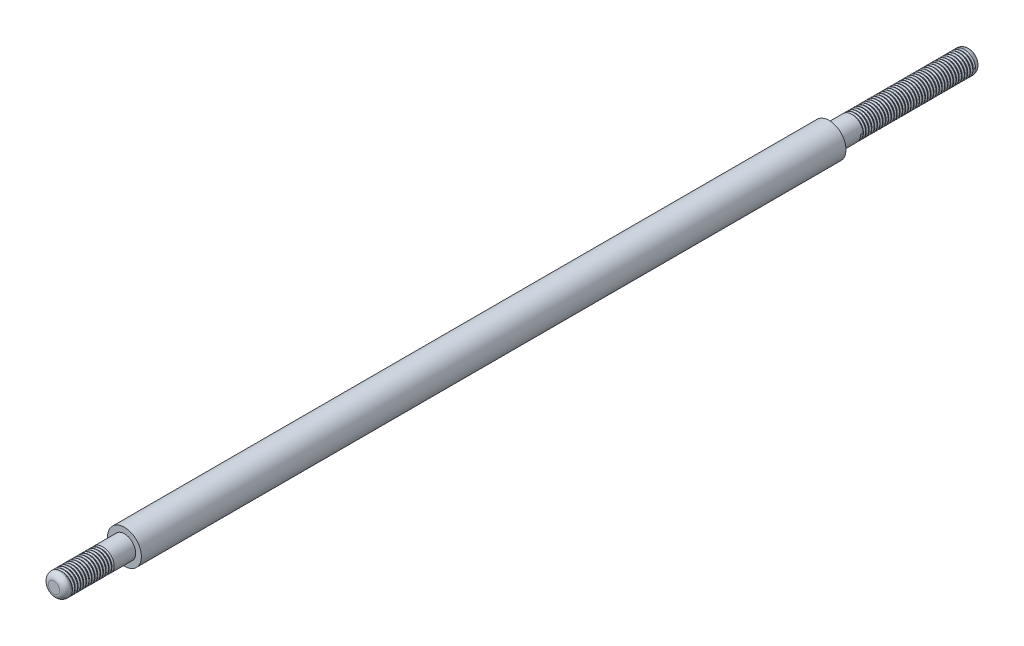
SolidWorks part; units mm, degrees
material "1023 碳钢板 (SS)"
ref_plane "前视基准面" through (0, 0, 0) normal (0, 0, 1) x (1, 0, 0)
ref_plane "上视基准面" through (0, 0, 0) normal (0, 1, 0) x (1, 0, 0)
ref_plane "右视基准面" through (0, 0, 0) normal (1, 0, 0) x (0, 0, -1)
sketch "草图1" plane through (0, 0, 0) normal (0, 0, 1) x (1, 0, 0)
  circle A0 centre (0, 0) radius 6
extrude "凸台-拉伸1" add sketch "草图1" along normal blind 250
sketch "草图2" plane through (0, 0, 250) normal (0, 0, 1) x (1, 0, 0)
  circle A0 centre (0, 0) radius 4
extrude "凸台-拉伸2" add sketch "草图2" along normal blind 25
sketch "草图3" plane through (0, 0, 0) normal (0, 0, -1) x (-1, 0, 0)
  circle A0 centre (0, 0) radius 4
extrude "凸台-拉伸3" add sketch "草图3" along normal blind 50
fillet "圆角1" radius 2 1 edges at (-4, 0, -50)
thread "螺纹线3" pitch 1 method cut profile "螺纹线轮廓3" start angle 0, offset 0, length 40, pitch 1, diameter 8
ref_plane "基准面3" through (4, 0, -48) normal (0, -1, 0) x (1, 0, 0)
sketch "螺纹线轮廓3" plane through (4, 0, -48) normal (0, -1, 0) x (1, 0, 0)
  line L0 (0, 0) -> (0, 1) construction
  line L11 (0, 0) -> (0, 0.875)
  line L12 (0, 0.875) -> (-0.5413, 0.5625)
  line L13 (-0.5413, 0.5625) -> (-0.5413, 0.3125)
  line L15 (-0.5413, 0.3125) -> (0, 0)
  line L17 (-0.5413, 0.4375) -> (0, 0.4375) construction
  point P2 (0, 0)
  dimension "Pitch" = 1
  dimension "Profile_Angle" = 60
  dimension "Profile_Land" = 0.25
  dimension "Profile_Height" = 0.5413
fillet "圆角2" radius 2 1 edges at (4, 0, 275)
thread "螺纹线4" pitch 1 method cut profile "螺纹线轮廓4" start angle 0, offset 0, length 15, pitch 1, diameter 8
ref_plane "基准面4" through (-4, 0, 273) normal (0, -1, 0) x (-1, 0, 0)
sketch "螺纹线轮廓4" plane through (-4, 0, 273) normal (0, -1, 0) x (-1, 0, 0)
  line L0 (0, 0) -> (0, 1) construction
  line L11 (0, 0) -> (0, 0.875)
  line L12 (0, 0.875) -> (-0.5413, 0.5625)
  line L13 (-0.5413, 0.5625) -> (-0.5413, 0.3125)
  line L15 (-0.5413, 0.3125) -> (0, 0)
  line L17 (-0.5413, 0.4375) -> (0, 0.4375) construction
  point P2 (0, 0)
  dimension "Pitch" = 1
  dimension "Profile_Angle" = 60
  dimension "Profile_Land" = 0.25
  dimension "Profile_Height" = 0.5413
